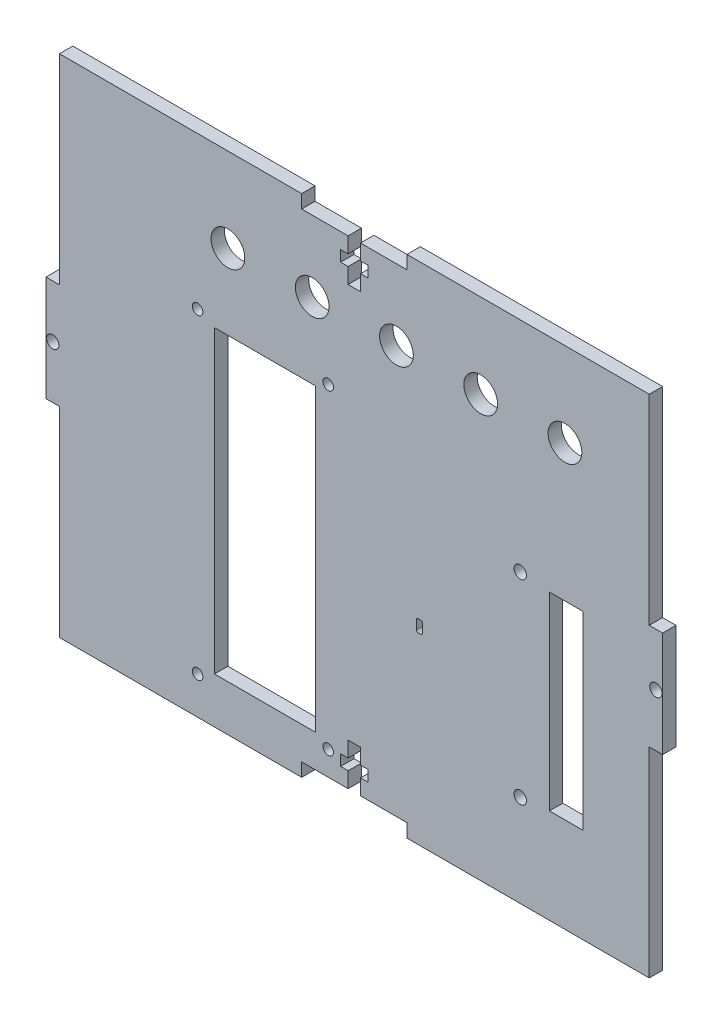
SolidWorks part; units mm, degrees
ref_plane "Front Plane" through (0, 0, 0) normal (0, 0, 1) x (1, 0, 0)
ref_plane "Top Plane" through (0, 0, 0) normal (0, 1, 0) x (1, 0, 0)
ref_plane "Right Plane" through (0, 0, 0) normal (1, 0, 0) x (0, 0, -1)
sketch "Sketch1" plane through (0, 0, 0) normal (0, 0, 1) x (1, 0, 0)
  line L0 (0, 60) -> (0, -60) construction
  line L1 (-70, 60) -> (70, 60)
  line L2 (-70, 60) -> (-70, -60)
  line L3 (-70, -60) -> (70, -60)
  line L4 (70, 60) -> (70, -60)
  line L5 (-70, 60) -> (70, -60) construction
  line L6 (-70, -60) -> (70, 60) construction
  line L7 (-70, 0) -> (70, 0) construction
  line L8 (-3.25, -50.525) -> (3.25, -50.525)
  line L9 (12.5, 60) -> (-12.5, 60)
  line L10 (12.5, 60) -> (12.5, 56.825)
  line L11 (12.5, 56.825) -> (-12.5, 56.825)
  line L12 (-12.5, 60) -> (-12.5, 56.825)
  line L13 (12.5, 60) -> (-12.5, 56.825) construction
  line L14 (12.5, 56.825) -> (-12.5, 60) construction
  line L15 (-1.47, 56.825) -> (1.47, 56.825)
  line L16 (-1.47, 56.825) -> (-1.47, 46.825)
  line L17 (-1.47, 46.825) -> (1.47, 46.825)
  line L18 (1.47, 56.825) -> (1.47, 46.825)
  line L19 (-1.47, 56.825) -> (1.47, 46.825) construction
  line L20 (-1.47, 46.825) -> (1.47, 56.825) construction
  line L21 (-3.25, 53.125) -> (3.25, 53.125)
  line L22 (-3.25, 53.125) -> (-3.25, 50.525)
  line L23 (-3.25, 50.525) -> (3.25, 50.525)
  line L24 (3.25, 53.125) -> (3.25, 50.525)
  line L25 (-3.25, 53.125) -> (3.25, 50.525) construction
  line L26 (-3.25, 50.525) -> (3.25, 53.125) construction
  line L27 (3.25, -53.125) -> (3.25, -50.525)
  line L28 (-3.25, -53.125) -> (3.25, -53.125)
  line L29 (-3.25, -53.125) -> (-3.25, -50.525)
  line L30 (-1.47, -46.825) -> (1.47, -46.825)
  line L31 (1.47, -56.825) -> (1.47, -46.825)
  line L32 (-1.47, -56.825) -> (1.47, -56.825)
  line L33 (-1.47, -56.825) -> (-1.47, -46.825)
  line L34 (12.5, -56.825) -> (-12.5, -56.825)
  line L35 (-12.5, -60) -> (-12.5, -56.825)
  line L36 (12.5, -60) -> (-12.5, -60)
  line L37 (12.5, -60) -> (12.5, -56.825)
  line L38 (73.175, -12.5) -> (70, -12.5)
  line L39 (-73.175, 12.5) -> (-70, 12.5)
  line L40 (-73.175, 12.5) -> (-73.175, -12.5)
  line L41 (-73.175, -12.5) -> (-70, -12.5)
  line L42 (-70, 12.5) -> (-70, -12.5)
  line L43 (-73.175, 12.5) -> (-70, -12.5) construction
  line L44 (-73.175, -12.5) -> (-70, 12.5) construction
  line L45 (70, 12.5) -> (70, -12.5)
  line L46 (73.175, 12.5) -> (70, 12.5)
  line L47 (73.175, 12.5) -> (73.175, -12.5)
  circle A0 centre (-71.5875, 0) radius 1.47
  circle A1 centre (71.5875, 0) radius 1.47
  point P0 (0, 0)
  point P10 (0, 58.4125)
  point P15 (0, 51.825)
  point P20 (0, 51.825)
  point P37 (-71.5875, 0)
  dimension "D11" = 2.94
  dimension "D1" = 120
  dimension "D2" = 140
  dimension "D3" = 3.175
  dimension "D4" = 10
  dimension "D5" = 2.94
  dimension "D6" = 25
  dimension "D7" = 6.5
  dimension "D8" = 2.6
  dimension "D9" = 6.3
  dimension "D10" = 3.175
extrude "Boss-Extrude1" add sketch "Sketch1" along normal mid plane 3.175 contours L21 L24 L23 L18 L17 L16 L22 L11 L12 L1 L2 L3 L4 L10 | L40 L39 L42 L41 | A0 | L38 L45 L46 L47 | A1 region at (0, 0, 0)
sketch "Sketch3" plane through (0, 0, -1.5875) normal (0, 0, -1) x (-1, 0, 0)
  line L0 (-9.6476, 0) -> (-9.6476, -15) construction
  line L5 (-9.6476, -15) -> (-19.2951, -15) construction
  line L6 (-50.3, 7.5) -> (-50.3, -22.5) construction
  line L7 (-46.3, 7.5) -> (-54.3, 7.5)
  line L8 (-46.3, 7.5) -> (-46.3, -37.5)
  line L9 (-46.3, -37.5) -> (-54.3, -37.5)
  line L10 (-54.3, 7.5) -> (-54.3, -37.5)
  line L11 (-48.7125, -40) -> (-48.7125, 10) construction
  line L12 (-51.8875, 10) -> (-51.8875, -40) construction
  line L13 (0, 0) -> (-19.2951, 0) construction
  dimension "D1" = 8
  dimension "D2" = 45
  dimension "D3" = 15
extrude "Cut-Extrude1" cut sketch "Sketch3" against normal through all
sketch "Sketch4" plane through (0, 0, -1.5875) normal (0, 0, -1) x (-1, 0, 0)
  line L0 (33.2, 21.2555) -> (33.2, -48.2445) construction
  line L1 (33.2, 22.1055) -> (9.2, 22.1055)
  line L2 (33.2, 22.1055) -> (33.2, -49.0945)
  line L3 (33.2, -49.0945) -> (9.2, -49.0945)
  line L4 (9.2, 22.1055) -> (9.2, -49.0945)
  line L5 (9.2, -48.2445) -> (9.2, 21.2555) construction
  line L6 (10.05, 22.1055) -> (16.7, 22.1055) construction
  line L7 (32.35, -49.0945) -> (10.05, -49.0945) construction
extrude "Cut-Extrude2" cut sketch "Sketch4" against normal through all
sketch "Sketch5" plane through (0, 0, -1.5875) normal (0, 0, -1) x (-1, 0, 0)
  line L0 (-15.1534, -16.25) -> (-15.7792, -16.25) construction
  line L1 (-15.7792, -13.75) -> (-15.1534, -13.75) construction
  line L2 (-14.9534, -13.95) -> (-14.9534, -16.05) construction
  line L3 (-15.1534, -16.25) -> (-15.7792, -16.25)
  line L4 (-15.7792, -13.75) -> (-15.1534, -13.75)
  line L5 (-14.9534, -13.95) -> (-14.9534, -16.05)
  line L6 (-15.1534, -16.45) -> (-15.7792, -16.45)
  line L7 (-15.7792, -13.55) -> (-15.1534, -13.55)
  line L8 (-14.7534, -13.95) -> (-14.7534, -16.05)
  arc A0 (-15.1534, -16.25) -> (-14.9534, -16.05) centre (-15.1534, -16.05) ccw construction
  arc A1 (-15.9775, -16.0753) -> (-15.7792, -16.25) centre (-15.7792, -16.05) ccw construction
  arc A2 (-15.9775, -13.9247) -> (-15.9775, -16.0753) centre (-7.5458, -15) ccw construction
  arc A3 (-15.7792, -13.75) -> (-15.9775, -13.9247) centre (-15.7792, -13.95) ccw construction
  arc A4 (-14.9534, -13.95) -> (-15.1534, -13.75) centre (-15.1534, -13.95) ccw construction
  arc A5 (-15.1534, -16.25) -> (-14.9534, -16.05) centre (-15.1534, -16.05) ccw
  arc A6 (-15.9775, -16.0753) -> (-15.7792, -16.25) centre (-15.7792, -16.05) ccw
  arc A7 (-15.9775, -13.9247) -> (-15.9775, -16.0753) centre (-7.5458, -15) ccw
  arc A8 (-15.7792, -13.75) -> (-15.9775, -13.9247) centre (-15.7792, -13.95) ccw
  arc A9 (-14.9534, -13.95) -> (-15.1534, -13.75) centre (-15.1534, -13.95) ccw
  arc A10 (-16.1759, -16.1006) -> (-15.7792, -16.45) centre (-15.7792, -16.05) ccw
  arc A11 (-16.1759, -13.8994) -> (-16.1759, -16.1006) centre (-7.5458, -15) ccw
  arc A12 (-15.7792, -13.55) -> (-16.1759, -13.8994) centre (-15.7792, -13.95) ccw
  arc A13 (-14.7534, -13.95) -> (-15.1534, -13.55) centre (-15.1534, -13.95) ccw
  arc A14 (-15.1534, -16.45) -> (-14.7534, -16.05) centre (-15.1534, -16.05) ccw
  dimension "D1" = 0.2
extrude "Cut-Extrude4" cut sketch "Sketch5" against normal through all contours L8 A14 L6 A10 A11 A12 L7 A13
sketch "Sketch6" plane through (0, 0, -1.5875) normal (0, 0, -1) x (-1, 0, 0)
  line L0 (-70, 40) -> (70, 40) construction
  line L1 (-70, 56.825) -> (-70, 12.5) construction
  line L2 (70, 60) -> (70, 12.5) construction
  line L3 (70, 60) -> (12.5, 60) construction
  line L4 (-50, 40) -> (-30, 40)
  line L5 (-30, 40) -> (-10, 40)
  line L6 (-10, 40) -> (10, 40)
  line L7 (10, 40) -> (30, 40)
  line L8 (-70, 60) -> (-70, 12.5) construction
  line L9 (-10, 40) -> (10, 40)
  line L10 (-30, 40) -> (-10, 40)
  line L11 (-50, 40) -> (-30, 40)
  line L12 (-70, 40) -> (-50, 40)
  circle A0 centre (30, 40) radius 4
  circle A1 centre (10, 40) radius 4
  circle A2 centre (-10, 40) radius 4
  circle A3 centre (-30, 40) radius 4
  circle A4 centre (-50, 40) radius 4
  dimension "D4" = 8
  dimension "D1" = 20
  dimension "D2" = 20
  dimension "D3" = 20
  dimension "D5" = 5
extrude "Cut-Extrude5" cut sketch "Sketch6" against normal through all contours A0 | A1 | A2 | A3 | A4
sketch "Sketch9" plane through (0, 0, 1.5875) normal (0, 0, 1) x (1, 0, 0)
  circle A0 centre (-37.2, 23.9055) radius 1.25 construction
  circle A1 centre (-6.2, 23.9055) radius 1.25 construction
  circle A2 centre (-6.2, -51.0945) radius 1.25 construction
  circle A3 centre (-37.2, -51.0945) radius 1.25 construction
  circle A4 centre (-37.2, 23.9055) radius 1.25
  circle A5 centre (-6.2, 23.9055) radius 1.25
  circle A6 centre (-6.2, -51.0945) radius 1.25
  circle A7 centre (-37.2, -51.0945) radius 1.25
  circle A8 centre (39.3875, 8.1613) radius 1.47 construction
  circle A9 centre (39.3875, -38.1613) radius 1.47 construction
  circle A10 centre (39.3875, 8.1613) radius 1.47
  circle A11 centre (39.3875, -38.1613) radius 1.47
extrude "Cut-Extrude6" cut sketch "Sketch9" against normal through all
sketch "Sketch10" plane through (0, 0, -1.5875) normal (0, 0, -1) x (-1, 0, 0)
  line L4 (50, 60) -> (50, -60) construction
  line L5 (70, 60) -> (12.5, 60) construction
  line L6 (70, -60) -> (12.5, -60) construction
  line L7 (70, 60) -> (70, 12.5) construction
  dimension "D1" = 20
sketch "Sketch11" plane through (0, 0, -1.5875) normal (0, 0, -1) x (-1, 0, 0)
  text T0 "Alden Dent PID Box" font "Century Gothic" height 9
